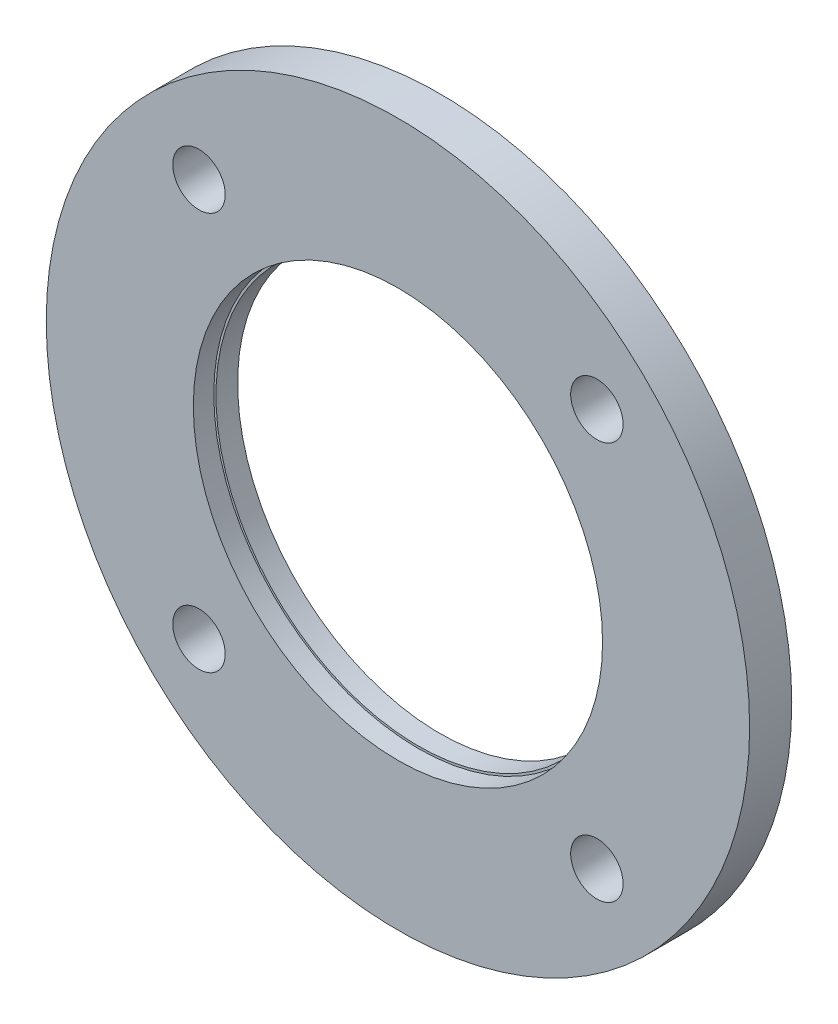
SolidWorks part; units mm, degrees
ref_plane "Front Plane" through (0, 0, 0) normal (0, 0, 1) x (1, 0, 0)
ref_plane "Top Plane" through (0, 0, 0) normal (0, 1, 0) x (1, 0, 0)
ref_plane "Right Plane" through (0, 0, 0) normal (1, 0, 0) x (0, 0, -1)
ref_axis "Z" through (0, 0, -0.1647) along (0, 0, 1)
sketch "Sketch1" plane through (0, 0, 0) normal (0, 1, 0) x (1, 0, 0)
  line L0 (-15.83, 0) -> (-27.5, 0)
  line L1 (-27.5, 0) -> (-27.5, -3.294)
  line L2 (-27.5, -3.294) -> (-16, -3.294)
  line L3 (-16, -3.294) -> (-16, -1.694)
  line L4 (-16, -1.694) -> (-15.83, -1.694)
  line L5 (-15.83, -1.694) -> (-15.83, 0)
  line L6 (0, -1.0245) -> (0, 4.9373) construction
  point P7 (0, 0)
  dimension "D1" = 1.6
  dimension "D2" = 32
  dimension "D3" = 0.17
  dimension "D4" = 1.694
  dimension "D5" = 55
revolve "Revolve1" add sketch "Sketch1" angle 360 about L6
sketch "Sketch2" plane through (0, 0, 0) normal (0, 0, 1) x (1, 0, 0)
  line L0 (-15.5563, 15.5563) -> (0, 0) construction
  line L1 (0, 0) -> (0, 34.6787) construction
  circle A0 centre (-15.5563, 15.5563) radius 2.05
  circle A1 centre (15.5563, 15.5563) radius 2.05
  circle A2 centre (15.5563, -15.5563) radius 2.05
  circle A3 centre (-15.5563, -15.5563) radius 2.05
  point P5 (-17.1511, 13.7782)
  point P13 (0, 0)
  dimension "D4" = 4.1
  dimension "D1" = 22
  dimension "D3" = 45
  dimension "D2" = 4
extrude "Cut-Extrude1" cut sketch "Sketch2" along normal through all
